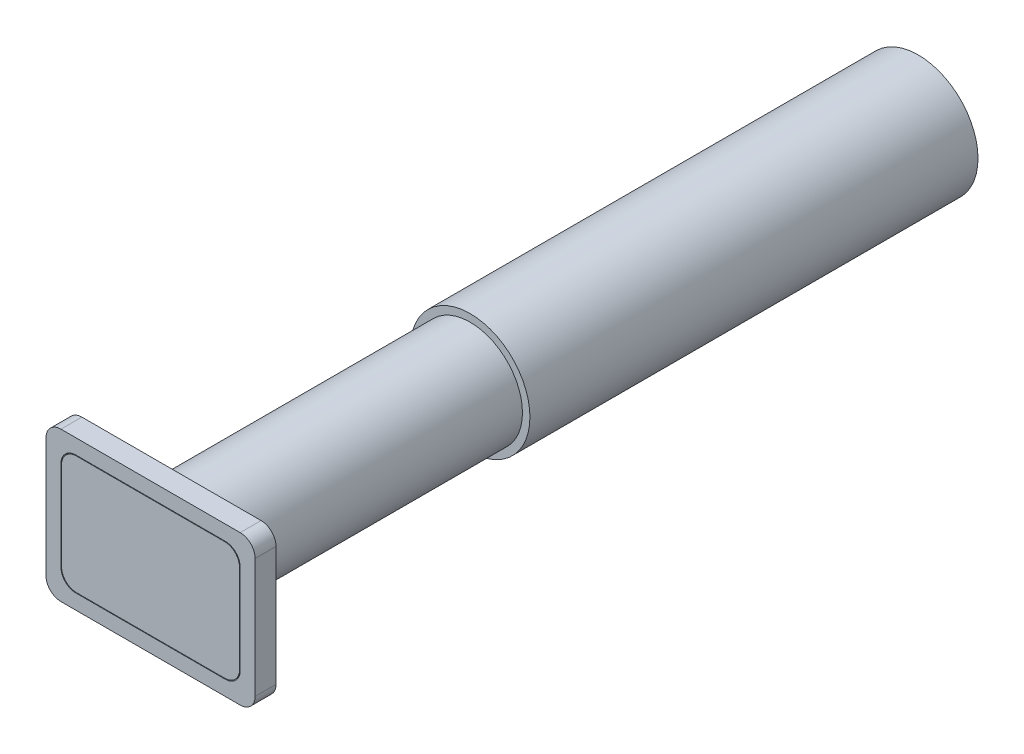
SolidWorks part; units mm, degrees
ref_plane "Front Plane" through (0, 0, 0) normal (0, 0, 1) x (1, 0, 0)
ref_plane "Top Plane" through (0, 0, 0) normal (0, 1, 0) x (1, 0, 0)
ref_plane "Right Plane" through (0, 0, 0) normal (1, 0, 0) x (0, 0, -1)
sketch "Sketch1" plane through (0, 0, 0) normal (0, 0, 1) x (1, 0, 0)
  circle A0 centre (0, 0) radius 25.4
  dimension "D1" = 50.8
extrude "Boss-Extrude1" add sketch "Sketch1" along normal blind 190.5
sketch "Sketch2" plane through (0, 0, 190.5) normal (0, 0, 1) x (1, 0, 0)
  circle A0 centre (0, 0) radius 22.225
  dimension "D1" = 44.45
extrude "Boss-Extrude2" add sketch "Sketch2" along normal blind 127
sketch "Sketch3" plane through (0, 0, 317.5) normal (0, 0, 1) x (1, 0, 0)
  line L1 (-38.1, 31.75) -> (38.1, 31.75)
  line L2 (-44.45, 25.4) -> (-44.45, -25.4)
  line L3 (-38.1, -31.75) -> (38.1, -31.75)
  line L4 (44.45, 25.4) -> (44.45, -25.4)
  arc A0 (38.1, 31.75) -> (44.45, 25.4) centre (38.1, 25.4) cw
  arc A1 (38.1, -31.75) -> (44.45, -25.4) centre (38.1, -25.4) ccw
  arc A2 (-44.45, -25.4) -> (-38.1, -31.75) centre (-38.1, -25.4) ccw
  arc A3 (-38.1, 31.75) -> (-44.45, 25.4) centre (-38.1, 25.4) ccw
  point P7 (44.45, 31.75)
  point P10 (44.45, -31.75)
  point P15 (-44.45, 31.75)
  dimension "D5" = 6.35
  dimension "D1" = 88.9
  dimension "D2" = 63.5
  dimension "D3" = 44.45
  dimension "D4" = 31.75
extrude "Boss-Extrude3" add sketch "Sketch3" along normal blind 8.89
sketch "Sketch4" plane through (0, 0, 326.39) normal (0, 0, 1) x (1, 0, 0)
  line L1 (-31.75, -25.4) -> (31.75, -25.4)
  line L2 (-38.1, -19.05) -> (-38.1, 19.05)
  line L3 (-31.75, 25.4) -> (31.75, 25.4)
  line L4 (38.1, -19.05) -> (38.1, 19.05)
  arc A0 (31.75, 25.4) -> (38.1, 19.05) centre (31.75, 19.05) cw
  arc A1 (31.75, -25.4) -> (38.1, -19.05) centre (31.75, -19.05) ccw
  arc A2 (-31.75, -25.4) -> (-38.1, -19.05) centre (-31.75, -19.05) cw
  arc A3 (-38.1, 19.05) -> (-31.75, 25.4) centre (-31.75, 19.05) cw
  point P4 (31.9354, 19.7115)
  point P8 (38.1, 25.4)
  point P11 (38.1, -25.4)
  point P16 (-38.1, 25.4)
  dimension "D5" = 6.35
  dimension "D1" = 76.2
  dimension "D2" = 50.8
  dimension "D3" = 25.4
  dimension "D4" = 38.1
extrude "Cut-Extrude1" cut sketch "Sketch4" against normal blind 6.35
ref_plane "Plane1" through (0, 0, 320.294) normal (0, 0, 1) x (1, 0, 0)
sketch "Sketch5" plane through (0, 0, 320.294) normal (0, 0, 1) x (1, 0, 0)
  line L1 (-31.496, 25.146) -> (31.496, 25.146)
  line L2 (-37.846, 18.796) -> (-37.846, -18.796)
  line L3 (-31.496, -25.146) -> (31.496, -25.146)
  line L4 (37.846, 18.796) -> (37.846, -18.796)
  arc A0 (31.496, 25.146) -> (37.846, 18.796) centre (31.496, 18.796) cw
  arc A1 (31.496, -25.146) -> (37.846, -18.796) centre (31.496, -18.796) ccw
  arc A2 (-37.846, -18.796) -> (-31.496, -25.146) centre (-31.496, -18.796) ccw
  arc A3 (-31.496, 25.146) -> (-37.846, 18.796) centre (-31.496, 18.796) ccw
  point P7 (51.692, -5.6383)
  point P8 (37.846, 25.146)
  point P13 (-37.846, -25.146)
  point P16 (-37.846, 25.146)
  dimension "D5" = 6.35
  dimension "D1" = 75.692
  dimension "D2" = 50.292
  dimension "D3" = 37.846
  dimension "D4" = 25.146
extrude "Boss-Extrude5" add sketch "Sketch5" along normal blind 6.096 separate body
